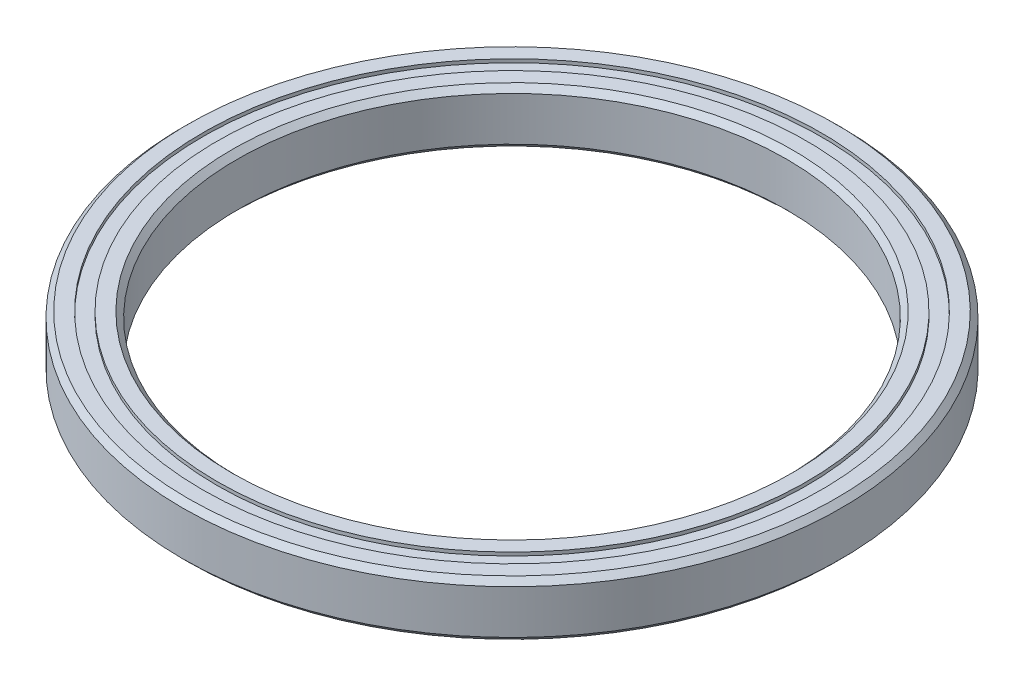
SolidWorks part; units mm, degrees
material "不锈钢 (铁素体)"
ref_plane "前视基准面" through (0, 0, 0) normal (0, 0, 1) x (1, 0, 0)
ref_plane "上视基准面" through (0, 0, 0) normal (0, 1, 0) x (1, 0, 0)
ref_plane "右视基准面" through (0, 0, 0) normal (1, 0, 0) x (0, 0, -1)
sketch "草图1" plane through (0, 0, 0) normal (0, 1, 0) x (1, 0, 0)
  circle A0 centre (0, 0) radius 40
  circle A1 centre (0, 0) radius 48
  dimension "D1" = 80
  dimension "D2" = 96
extrude "凸台-拉伸1" add sketch "草图1" along normal blind 8
sketch "草图2" plane through (0, 8, 0) normal (0, 1, 0) x (1, 0, 0)
  circle A0 centre (0, 0) radius 42.95
  circle A1 centre (0, 0) radius 45.05
  dimension "D1" = 85.9
  dimension "D2" = 90.1
extrude "切除-拉伸1" cut sketch "草图2" against normal blind 0.5
extrude "切除-拉伸2" cut sketch "草图2<2>" along normal blind 0.5 from surface starting at face at (0, 0, 48)
sketch "草图2<2>" plane through (0, 8, 0) normal (0, 1, 0) x (1, 0, 0) same geometry as "草图2"
chamfer "倒角1" distance 0.8 angle 45 4 edges at (0, 0, 40) (0, 8, 40) (0, 0, 48) (0, 8, 48)
